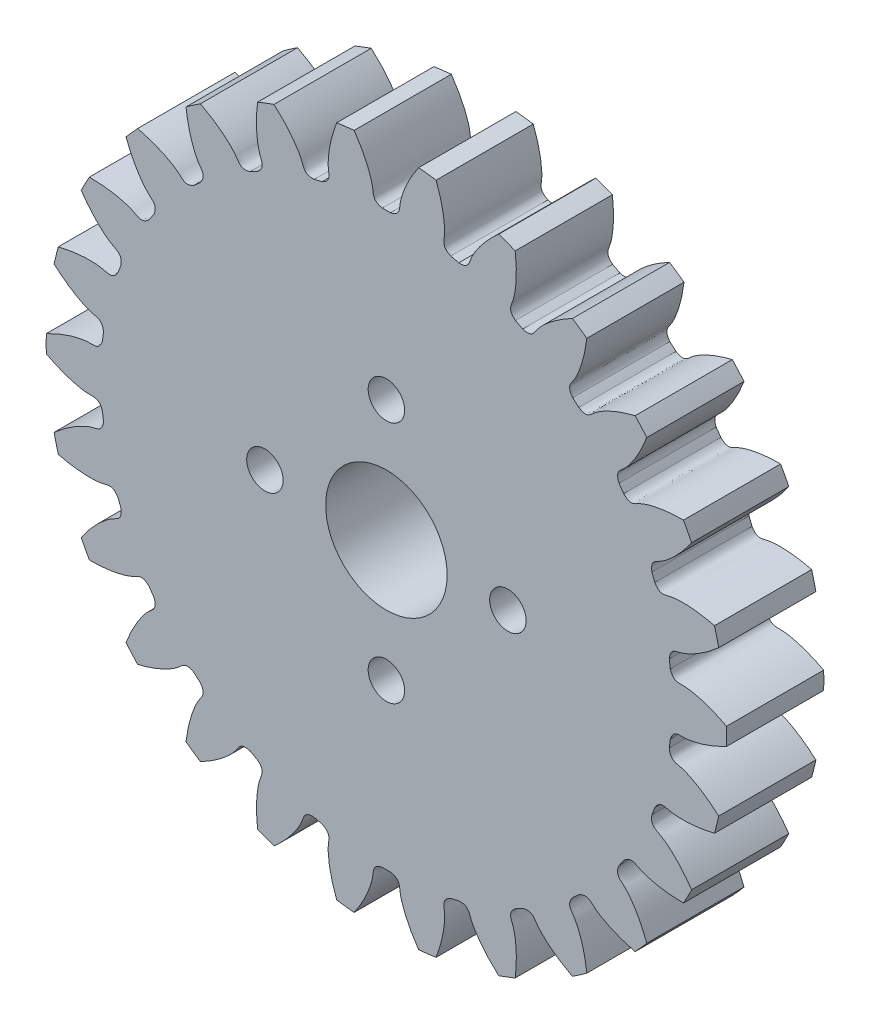
SolidWorks part; units mm, degrees
material "6061 合金"
ref_plane "前视基准面" through (0, 0, 0) normal (0, 0, 1) x (1, 0, 0)
ref_plane "上视基准面" through (0, 0, 0) normal (0, 1, 0) x (1, 0, 0)
ref_plane "右视基准面" through (0, 0, 0) normal (1, 0, 0) x (0, 0, -1)
sketch "草图1" plane through (0, 0, 0) normal (0, 0, 1) x (1, 0, 0)
  circle A0 centre (0, 0) radius 28
extrude "凸台-拉伸1" add sketch "草图1" along normal blind 8
ref_axis "基准轴1" through (0, 0, 8) along (0, 0, -1)
sketch "草图2" plane through (0, 0, 0) normal (0, 0, 1) x (1, 0, 0)
  line L0 (0, 0) -> (0, 28) construction
  circle A0 centre (0, 0) radius 28 construction
  arc A1 (0.3342, 23.4976) -> (-0.3342, 23.4976) centre (0, 0) ccw
  arc A2 (6.5898, 31.8709) -> (-6.5898, 31.8709) centre (0, 0) ccw
  spline S0 degree 3 poles (0.3342, 23.4976) (1.1262, 23.6476) (1.0607, 24.1159) (1.1348, 24.5844) (1.1459, 24.6469) (1.1602, 24.7188) (1.178, 24.7999) (1.1998, 24.8902) (1.2258, 24.9895) (1.2564, 25.0976) (1.292, 25.2145) (1.333, 25.3399) (1.3797, 25.4737) (1.4325, 25.6157) (1.4917, 25.7657) (1.5576, 25.9235) (1.6307, 26.0889) (1.7111, 26.2617) (1.7993, 26.4416) (1.8955, 26.6283) (2.0002, 26.8218) (2.1134, 27.0216) (2.2357, 27.2275) (2.3671, 27.4392) (2.5082, 27.6564) (2.659, 27.8789) (2.8198, 28.1063) (2.991, 28.3383) (3.1728, 28.5745) (3.3653, 28.8147) (3.5689, 29.0586) (3.7837, 29.3056) (4.01, 29.5556) (4.2479, 29.8081) (4.4977, 30.0628) (4.7595, 30.3193) (5.0335, 30.5772) (5.3199, 30.8361) (5.6187, 31.0956) (6.039, 31.4461) (6.366, 31.7024) (6.5898, 31.8709) knots 0 0 0 0 0.122665 0.127715 0.133684 0.14057 0.148375 0.157098 0.166739 0.177298 0.188775 0.201171 0.214485 0.228717 0.243867 0.259935 0.276922 0.294827 0.31365 0.333391 0.35405 0.375628 0.398124 0.421538 0.44587 0.47112 0.497289 0.524375 0.55238 0.581303 0.611145 0.641904 0.673582 0.706178 0.739692 0.774124 0.809475 0.845743 0.88293 0.921035 1 1 1 1
  spline S1 degree 3 poles (-0.3342, 23.4976) (-1.1262, 23.6476) (-1.0607, 24.1159) (-1.1348, 24.5844) (-1.1459, 24.6469) (-1.1602, 24.7188) (-1.178, 24.7999) (-1.1998, 24.8902) (-1.2258, 24.9895) (-1.2564, 25.0976) (-1.292, 25.2145) (-1.333, 25.3399) (-1.3797, 25.4737) (-1.4325, 25.6157) (-1.4917, 25.7657) (-1.5576, 25.9235) (-1.6307, 26.0889) (-1.7111, 26.2617) (-1.7993, 26.4416) (-1.8955, 26.6283) (-2.0002, 26.8218) (-2.1134, 27.0216) (-2.2357, 27.2275) (-2.3671, 27.4392) (-2.5082, 27.6564) (-2.659, 27.8789) (-2.8198, 28.1063) (-2.991, 28.3383) (-3.1728, 28.5745) (-3.3653, 28.8147) (-3.5689, 29.0586) (-3.7837, 29.3056) (-4.01, 29.5556) (-4.2479, 29.8081) (-4.4977, 30.0628) (-4.7595, 30.3193) (-5.0335, 30.5772) (-5.3199, 30.8361) (-5.6187, 31.0956) (-6.039, 31.4461) (-6.366, 31.7024) (-6.5898, 31.8709) knots 0 0 0 0 0.122665 0.127715 0.133684 0.14057 0.148375 0.157098 0.166739 0.177298 0.188775 0.201171 0.214485 0.228717 0.243867 0.259935 0.276922 0.294827 0.31365 0.333391 0.35405 0.375628 0.398124 0.421538 0.44587 0.47112 0.497289 0.524375 0.55238 0.581303 0.611145 0.641904 0.673582 0.706178 0.739692 0.774124 0.809475 0.845743 0.88293 0.921035 1 1 1 1
extrude "切除-拉伸1" cut sketch "草图2" along normal through all
pattern_circular "阵列(圆周)1" count 26 over 360 about axis through (0, 0, 8) along (0, 0, -1) of "切除-拉伸1"
sketch "草图3" plane through (0, 0, 0) normal (0, 0, 1) x (1, 0, 0)
  circle A0 centre (0, 0) radius 26 construction
  dimension "Dn" = 52
sketch "草图4" plane through (0, 0, 8) normal (0, 0, 1) x (1, 0, 0)
  circle A0 centre (0, 0) radius 5
  circle A1 centre (0, 0) radius 10 construction
  circle A2 centre (0, 10) radius 1.5
  circle A3 centre (10, 0) radius 1.5
  circle A4 centre (0, -10) radius 1.5
  circle A5 centre (-10, 0) radius 1.5
  point P15 (0, 0)
  dimension "D1" = 10
  dimension "D2" = 20
  dimension "D3" = 3
  dimension "D4" = 4
extrude "切除-拉伸2" cut sketch "草图4" against normal blind 10
